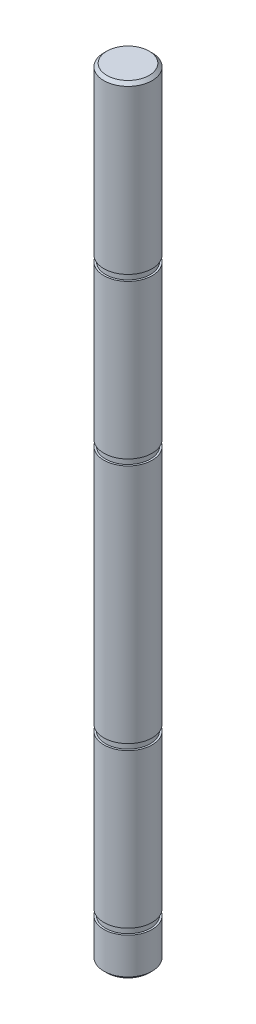
SolidWorks part; units mm, degrees
material "1.7225 (42CrMo4)"
ref_plane "Ebene vorne" through (0, 0, 0) normal (0, 0, 1) x (1, 0, 0)
ref_plane "Ebene oben" through (0, 0, 0) normal (0, 1, 0) x (1, 0, 0)
ref_plane "Ebene rechts" through (0, 0, 0) normal (1, 0, 0) x (0, 0, -1)
sketch "Skizze1" plane through (0, 0, 0) normal (0, 1, 0) x (1, 0, 0)
  circle A0 centre (0, 0) radius 4
  dimension "D1" = 8
extrude "Aufsatz-Linear austragen1" add sketch "Skizze1" along normal blind 117
sketch "Skizze4" plane through (0, 117, 0) normal (0, 1, 0) x (1, 0, 0)
  circle A0 centre (0, 0) radius 4
  dimension "3" = 8
extrude "Aufsatz-Linear austragen3" add sketch "Skizze4" along normal blind 7
sketch "Skizze5" plane through (0, 0, 0) normal (0, -1, 0) x (1, 0, 0)
  circle A0 centre (0, 0) radius 4
  dimension "D1" = 8
extrude "Aufsatz-Linear austragen4" add sketch "Skizze5" along normal blind 4.87
ref_plane "Ebene1" through (0, 95.5, 0) normal (0, 1, 0) x (1, 0, 0)
ref_plane "Ebene2" through (0, 2.63, 0) normal (0, -1, 0) x (-1, 0, 0)
sketch "Skizze6" plane through (0, 2.63, 0) normal (0, -1, 0) x (-1, 0, 0)
  circle A0 centre (0, 0) radius 4
  circle A1 centre (0, 0) radius 3.7
  dimension "D1" = 7.4
  dimension "D2" = 8
extrude "Schnitt-Linear austragen1" cut sketch "Skizze6" along normal blind 1
sketch "Skizze7" plane through (0, 95.5, 0) normal (0, 1, 0) x (1, 0, 0)
  circle A0 centre (0, 0) radius 4
  circle A1 centre (0, 0) radius 3.7
  circle A3 centre (0, 0) radius 4 construction
  dimension "D1" = 7.4
extrude "Schnitt-Linear austragen2" cut sketch "Skizze7" along normal blind 1
ref_plane "Ebene3" through (0, 70, 0) normal (0, 1, 0) x (1, 0, 0)
ref_plane "Ebene4" through (0, 28.13, 0) normal (0, -1, 0) x (-1, 0, 0)
sketch "Skizze8" plane through (0, 28.13, 0) normal (0, -1, 0) x (-1, 0, 0)
  circle A0 centre (0, 0) radius 4
  circle A1 centre (0, 0) radius 3.7
  circle A3 centre (0, 0) radius 4 construction
  dimension "D1" = 7.4
extrude "Schnitt-Linear austragen3" cut sketch "Skizze8" against normal blind 1
sketch "Skizze9" plane through (0, 70, 0) normal (0, 1, 0) x (1, 0, 0)
  circle A0 centre (0, 0) radius 4
  circle A1 centre (0, 0) radius 3.7
  circle A3 centre (0, 0) radius 4 construction
  dimension "D1" = 7.4
extrude "Schnitt-Linear austragen4" cut sketch "Skizze9" against normal blind 1
chamfer "Fase1" distance 0.5 angle 45 2 edges at (0, -4.87, -4) (0, 124, 4)
